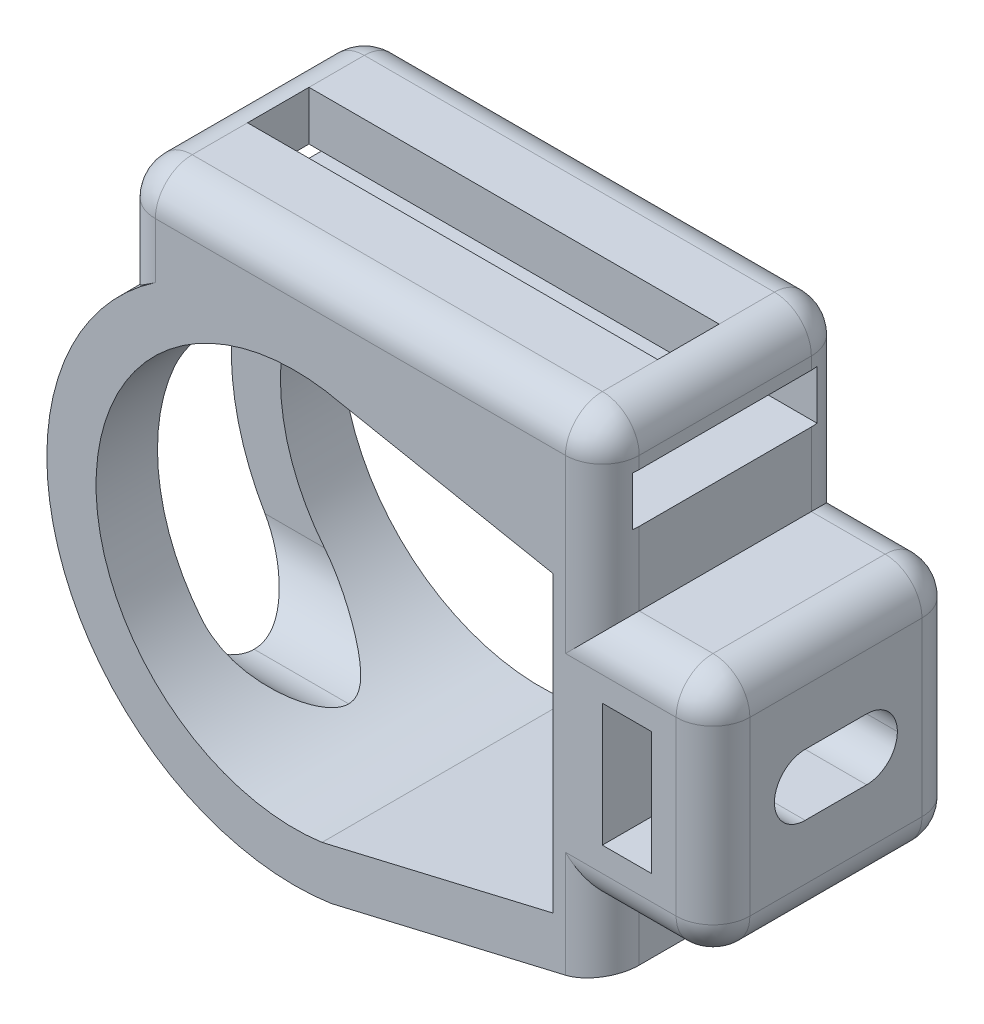
SolidWorks part; units mm, degrees
ref_plane "Alzado" through (0, 0, 0) normal (0, 0, 1) x (1, 0, 0)
ref_plane "Planta" through (0, 0, 0) normal (0, 1, 0) x (1, 0, 0)
ref_plane "Vista lateral" through (0, 0, 0) normal (1, 0, 0) x (0, 0, -1)
sketch "Croquis2" plane through (0, 0, 0) normal (0, 0, 1) x (1, 0, 0)
  line L0 (-51.9511, -1.694) -> (-49.9511, -1.694)
  line L1 (-49.9511, -1.694) -> (-51.9511, -1.694)
  line L2 (-1.9511, -10.694) -> (-1.9511, -41.694)
  line L3 (-1.9511, -41.694) -> (-51.9511, -41.694) construction
  line L4 (-51.9511, -1.694) -> (-51.9511, -41.694) construction
  line L5 (-49.9511, -1.694) -> (-49.9511, -11.294)
  line L6 (-49.9511, -11.294) -> (-36.9511, -11.294)
  line L7 (-36.9511, -11.294) -> (-36.9511, -9.294)
  line L8 (-36.9511, -9.294) -> (-31.9511, -9.294)
  line L9 (-31.9511, -9.294) -> (-31.9511, -11.994)
  line L10 (-31.9511, -11.994) -> (-17.3111, -11.994)
  line L11 (-17.3111, -11.994) -> (-17.3111, -7.694)
  line L12 (-17.3111, -7.694) -> (-24.3111, -7.694)
  line L13 (-24.3111, -7.694) -> (-24.3111, -4.694)
  line L14 (-24.3111, -4.694) -> (-14.3111, -4.694)
  line L15 (-14.3111, -4.694) -> (-14.3111, -10.694)
  line L16 (-14.3111, -10.694) -> (-1.9511, -10.694)
  line L17 (-1.9511, -41.694) -> (-4.5642, -41.694)
  line L18 (-4.5642, -41.694) -> (-4.5642, -19.454)
  line L19 (-4.5642, -19.454) -> (-22.3242, -19.454) construction
  line L20 (-22.3242, -41.694) -> (-22.3242, -15.394) construction
  line L21 (-4.5642, -19.454) -> (-22.3242, -15.394)
  line L22 (-42.1842, -30.694) -> (-40.1642, -30.694)
  line L23 (-22.3242, -15.394) -> (-26.7442, -15.394) construction
  line L24 (-42.1842, -41.694) -> (-42.1842, -30.694) construction
  line L25 (-40.1642, -41.694) -> (-40.1642, -30.694) construction
  line L26 (-26.7442, -15.394) -> (-26.7442, -15.354)
  line L27 (-22.3242, -15.394) -> (-26.7442, -15.354)
  line L28 (-40.1642, -30.694) -> (-26.7442, -15.354) construction
  arc A0 (-40.1642, -30.694) -> (-26.7442, -15.354) centre (-26.4173, -29.1801) cw
  dimension "D1" = 2
  dimension "D2" = 50
  dimension "D3" = 40
  dimension "D4" = 9.6
  dimension "D5" = 13
  dimension "D6" = 2
  dimension "D7" = 5
  dimension "D8" = 2.7
  dimension "D9" = 14.64
  dimension "D10" = 4.3
  dimension "D11" = 3
  dimension "D12" = 10
  dimension "D13" = 6
  dimension "D14" = 12.36
  dimension "D15" = 22.24
  dimension "D16" = 17.76
  dimension "D17" = 26.3
  dimension "D18" = 35.6
  dimension "D19" = 2.02
  dimension "D20" = 11
  dimension "D21" = 4.42
  dimension "D22" = 0.04
sketch "Croquis3" plane through (0, 0, 0) normal (0, 0, 1) x (1, 0, 0)
  line L218 (-8.1572, 2.8211) -> (-26.7313, 6.4418)
  line L219 (-8.1572, 2.8211) -> (-8.1572, -21.0951)
  line L220 (-8.1572, -21.0951) -> (-26.9615, -25.5138)
  line L238 (-4.1572, -24.2641) -> (-26.2158, -29.4475)
  line L239 (-4.1572, 6.1166) -> (-4.1572, -24.2641) construction
  line L250 (-43.5211, 4.6515) -> (-43.5211, 14.6515)
  line L251 (-43.5211, 14.6515) -> (-4.1572, 14.6515)
  line L253 (-4.1572, -24.2641) -> (-4.1572, 14.6515)
  line L277 (-4.1572, 6.1166) -> (-26.0389, 10.3821) construction
  arc A14 (-26.9615, -25.5138) -> (-26.7313, 6.4418) centre (-29.1957, -9.5191) cw
  arc A17 (-26.2158, -29.4475) -> (-43.5211, 4.6515) centre (-29.1957, -9.5191) cw
  arc A21 (-26.2158, -29.4475) -> (-26.0389, 10.3821) centre (-29.1957, -9.5191) cw construction
  dimension "D18" = 18.8042
  dimension "D15" = 18.574
  dimension "D3" = 10
  dimension "D29" = 16.15
  dimension "D9" = 4
  dimension "D21" = 23.9161
extrude "Saliente-Extruir1" add sketch "Croquis3" along normal blind 20 contours L238 A17 L250 L251 L253 | A14 L218 L219 L220
sketch "Croquis11" plane through (0, 0, 0) normal (0, 0, -1) x (-1, 0, 0)
  line L1 (0.1572, -9.3063) -> (-4.8428, -9.3063) construction
  line L2 (-4.8428, -19.3063) -> (-4.8428, 0.6937)
  line L3 (-4.8428, 0.6937) -> (4.1572, 0.6937)
  line L4 (4.1572, 0.6937) -> (4.1572, -4.3063)
  line L5 (4.1572, -4.3063) -> (0.1572, -4.3063)
  line L6 (0.1572, -4.3063) -> (0.1572, -14.3063)
  line L10 (4.1572, -9.3063) -> (2.5695, -9.3063) construction
  line L12 (-4.8428, -19.3063) -> (4.1572, -19.3063)
  line L13 (4.1572, -19.3063) -> (4.1572, -14.3063)
  line L14 (4.1572, -14.3063) -> (0.1572, -14.3063)
  dimension "D1" = 9
  dimension "D2" = 5
  dimension "D3" = 5
  dimension "D5" = 4
extrude "Saliente-Extruir2" add sketch "Croquis11" along direction (0, 0, -1) on the side against the normal up to surface (20 mm away) contours L13 L14 L6 L5 L4 L3 L2 L12 up to face at (-22.1265, -9.3032, 20)
sketch "Croquis12" plane through (4.8428, 0, 0) normal (1, 0, 0) x (0, 0, -1)
  line L1 (-20, 0.6937) -> (-20, -19.3063) construction
  line L2 (0, -19.3063) -> (0, 0.6937) construction
  line L3 (0, -19.3063) -> (0, 0.6937) construction
  line L5 (-15, -11.8063) -> (-5, -11.8063)
  line L8 (-5, -6.8063) -> (-15, -6.8063)
  line L9 (-15, -6.8063) -> (-15, -11.8063)
  line L11 (-5, -11.8063) -> (-5, -6.8063)
  point P2 (0, -9.3063)
  point P4 (-5, -9.3063)
  dimension "D1" = 5
  dimension "D2" = 5
  dimension "D3" = 5
extrude "Cortar-Extruir12" cut sketch "Croquis12" against normal up to surface (13 mm away) contours L11 L8 L9 L5 up to face at (-8.1572, -9.137, 10)
fillet "Redondeo1" radius 2.5 8 edges at (2.3428, -6.8063, 5) (2.3428, -6.8063, 15) (-6.1572, -11.8063, 5) (-6.1572, -6.8063, 5) (-6.1572, -11.8063, 15) (-6.1572, -6.8063, 15) (2.3428, -11.8063, 5) (2.3428, -11.8063, 15)
ref_plane "Plano1" through (-48.1572, 0, 0) normal (-1, 0, 0) x (0, 0, 1)
sketch "Croquis16" plane through (-48.1572, 0, 0) normal (-1, 0, 0) x (0, 0, 1)
  line L13 (5, 2.0572) -> (5, -24.6691)
  line L16 (0, 4.6515) -> (0, -29.6691) construction
  line L18 (20, -29.6691) -> (20, 4.6515) construction
  line L19 (5, 2.0572) -> (15, 2.0572)
  line L20 (5, 2.0572) -> (5, -24.6691)
  line L21 (5, -24.6691) -> (15, -24.6691)
  line L22 (15, 2.0572) -> (15, -24.6691)
  line L24 (0, -29.6691) -> (20, -29.6691) construction
  point P0 (25, 5.245)
  point P10 (24.9007, -25.4691)
  dimension "D3" = 5
  dimension "D4" = 26.7262
  dimension "D5" = 5
  dimension "D6" = 5
extrude "Cortar-Extruir17" cut sketch "Croquis16" against normal mid plane 40 contours L22 L19 L13 L21 region at (-48.1572, -11.306, 10)
fillet "Redondeo2" radius 5 4 edges at (-38.6357, -24.6691, 5) (-38.6357, -24.6691, 15) (-43.0727, 2.0572, 15) (-43.0727, 2.0572, 5)
sketch "Croquis21" plane through (-43.5211, 0, 0) normal (-1, 0, 0) x (0, 0, 1)
  line L0 (10, 4.6515) -> (10, 6.6515) construction
  line L1 (2.5, 10.6515) -> (17.5, 10.6515)
  line L2 (2.5, 10.6515) -> (2.5, 6.6515)
  line L3 (2.5, 6.6515) -> (17.5, 6.6515)
  line L4 (17.5, 10.6515) -> (17.5, 6.6515)
  line L5 (20, 4.6515) -> (0, 4.6515) construction
  point P8 (10, 6.6515)
  dimension "D1" = 4
  dimension "D2" = 15
  dimension "D3" = 2
extrude "Cortar-Extruir18" cut sketch "Croquis21" against normal up to next
fillet "Redondeo3" radius 3 18 edges at (-43.5211, 14.6515, 10) (-23.8392, 14.6515, 0) (-23.8392, 14.6515, 20) (-4.1572, 14.6515, 10) (4.8428, -9.3063, 0) (0.3428, -19.3063, 20) (0.3428, 0.6937, 20) (4.8428, -19.3063, 10) (4.8428, 0.6937, 10) (4.8428, -9.3063, 20) (-4.1572, -21.7852, 20) (-4.1572, -21.7852, 0) (0.3428, -19.3063, 0) (0.3428, 0.6937, 0) (-4.1572, 7.6726, 0) (-4.1572, 7.6726, 20) (-43.5211, 9.6515, 0) (-43.5211, 9.6515, 20)
sketch "Croquis22" plane through (0, 14.6515, 0) normal (0, 1, 0) x (1, 0, 0)
  line L0 (-40.5211, -3) -> (-40.5211, -17) construction
  line L1 (-40.5211, -7.5) -> (-7.1572, -7.5)
  line L2 (-40.5211, -7.5) -> (-40.5211, -12.5)
  line L3 (-40.5211, -12.5) -> (-7.1572, -12.5)
  line L4 (-7.1572, -7.5) -> (-7.1572, -12.5)
  line L5 (-7.1572, -17) -> (-7.1572, -3) construction
  point P8 (-40.5211, -10)
  point P9 (-40.5211, -10)
  dimension "D1" = 5
extrude "Cortar-Extruir20" cut sketch "Croquis22" against normal up to surface (4 mm away) contours L1 L4 L3 L2 up to face at (-23.8392, 10.6515, 10)
